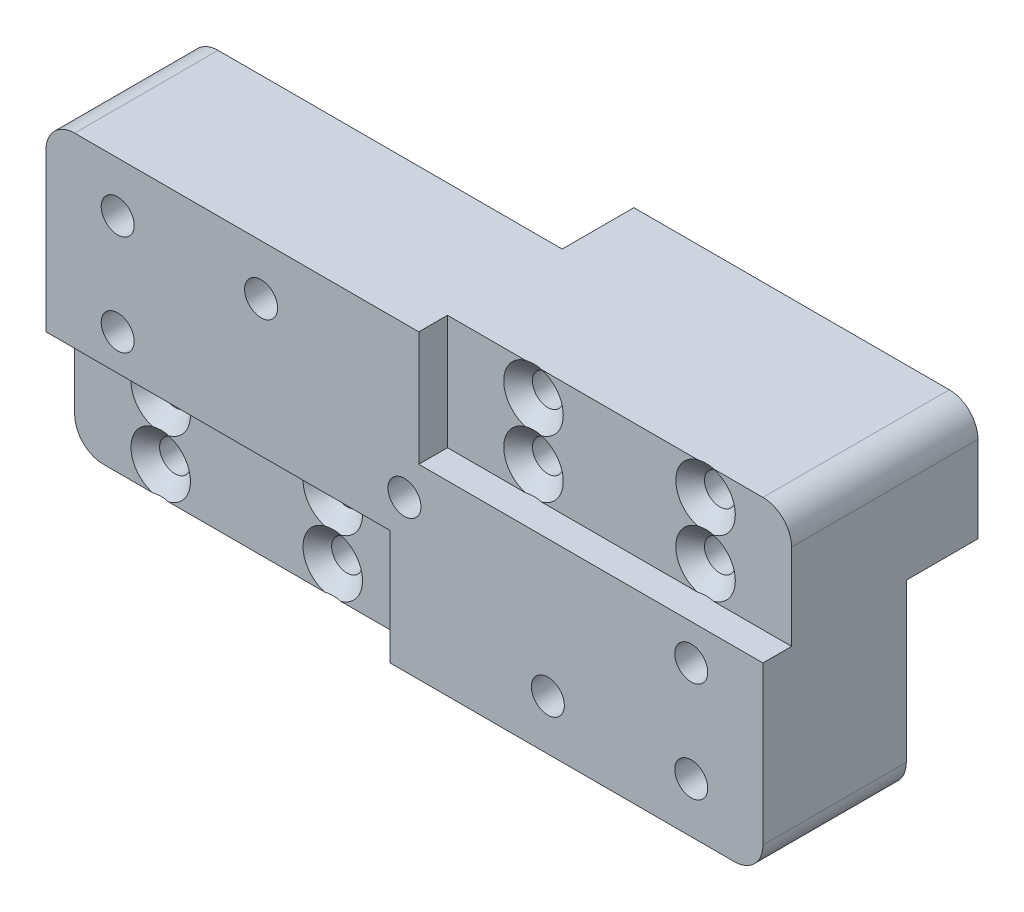
SolidWorks part; units mm, degrees
ref_plane "Front Plane" through (0, 0, 0) normal (0, 0, 1) x (1, 0, 0)
ref_plane "Top Plane" through (0, 0, 0) normal (0, 1, 0) x (1, 0, 0)
ref_plane "Right Plane" through (0, 0, 0) normal (1, 0, 0) x (0, 0, -1)
sketch "Sketch1" plane through (0, 0, 0) normal (0, 0, 1) x (1, 0, 0)
  line L0 (17.5, 10.5204) -> (17.5, 2.5204) construction
  line L1 (-20.5, -2.4796) -> (3.5, -2.4796)
  line L2 (-20.5, -2.4796) -> (-20.5, -10.4796)
  line L3 (-20.5, -10.4796) -> (3.5, -10.4796)
  line L4 (3.5, -2.4796) -> (3.5, -10.4796)
  line L5 (5.5, 10.5204) -> (29.5, 10.5204)
  line L6 (5.5, 10.5204) -> (5.5, 2.5204)
  line L7 (5.5, 2.5204) -> (29.5, 2.5204)
  line L8 (29.5, 10.5204) -> (29.5, 2.5204)
  line L9 (17.5, 6.5204) -> (5.5, 6.5204) construction
  line L10 (-8.5, -10.4796) -> (-8.5, -2.4796) construction
  line L11 (-8.5, -6.4796) -> (3.5, -6.4796) construction
  circle A0 centre (11.5, 8.5204) radius 1.075
  circle A2 centre (11.5, 4.5204) radius 1.075
  circle A3 centre (23.5, 4.5204) radius 1.075
  circle A5 centre (23.5, 8.5204) radius 1.075
  circle A7 centre (-14.5, -4.4796) radius 1.075
  circle A8 centre (-2.5, -8.4796) radius 1.075
  circle A11 centre (-14.5, -8.4796) radius 1.075
  circle A12 centre (-2.5, -4.4796) radius 1.075
  dimension "D7" = 2.15
  dimension "D15" = 2.15
  dimension "D16" = 2.15
  dimension "D17" = 2.15
  dimension "D1" = 8
  dimension "D2" = 8
  dimension "D3" = 2
  dimension "D4" = 24
  dimension "D5" = 24
  dimension "D6" = 5
  dimension "D9" = 6
  dimension "D10" = 2
  dimension "D13" = 2
extrude "Boss-Extrude1" add sketch "Sketch1" along normal blind 5
sketch "Sketch2" plane through (0, 0, 5) normal (0, 0, 1) x (1, 0, 0)
  line L1 (-20.5, -10.4796) -> (29.5, -10.4796)
  line L2 (-20.5, -10.4796) -> (-20.5, 10.5204)
  line L3 (-20.5, 10.5204) -> (29.5, 10.5204)
  line L4 (-20.5, -2.4796) -> (-20.5, -10.4796)
  line L5 (-20.5, -10.4796) -> (3.5, -10.4796)
  line L6 (3.5, -10.4796) -> (3.5, -2.4796)
  line L7 (3.5, -2.4796) -> (-20.5, -2.4796)
  line L8 (-20.5, -2.4796) -> (-20.5, -10.4796)
  line L9 (-20.5, -10.4796) -> (3.5, -10.4796)
  line L10 (3.5, -10.4796) -> (3.5, -2.4796)
  line L11 (3.5, -2.4796) -> (-20.5, -2.4796)
  line L12 (5.5, 10.5204) -> (5.5, 2.5204)
  line L13 (5.5, 2.5204) -> (29.5, 2.5204)
  line L14 (29.5, 2.5204) -> (29.5, 10.5204)
  line L15 (29.5, 10.5204) -> (5.5, 10.5204)
  line L16 (5.5, 10.5204) -> (5.5, 2.5204)
  line L17 (5.5, 2.5204) -> (29.5, 2.5204)
  line L18 (29.5, 2.5204) -> (29.5, 10.5204)
  line L19 (29.5, 10.5204) -> (5.5, 10.5204)
  line L20 (29.5, -10.4796) -> (29.5, 10.5204)
  circle A0 centre (-14.5, -8.4796) radius 1.075 construction
  circle A2 centre (-14.5, -4.4796) radius 1.075 construction
  circle A3 centre (-2.5, -8.4796) radius 1.075 construction
  circle A7 centre (11.5, 8.5204) radius 1.075 construction
  circle A8 centre (11.5, 4.5204) radius 1.075 construction
  circle A9 centre (23.5, 8.5204) radius 1.075 construction
  circle A11 centre (23.5, 4.5204) radius 1.075 construction
  circle A12 centre (23.5, 4.5204) radius 1.075
  circle A14 centre (23.5, 8.5204) radius 1.075
  circle A15 centre (11.5, 4.5204) radius 1.075
  circle A16 centre (11.5, 8.5204) radius 1.075
  circle A20 centre (-2.5, -8.4796) radius 1.075
  circle A21 centre (-14.5, -4.4796) radius 1.075
  circle A23 centre (-14.5, -8.4796) radius 1.075
  circle A24 centre (-2.5, -4.4796) radius 1.075 construction
  circle A25 centre (-2.5, -4.4796) radius 1.075
  circle M10 centre (-14.5, -8.4796) radius 1.075
  circle M11 centre (-14.5, -4.4796) radius 1.075
  line M12 (-20.5, -2.4796) -> (-20.5, -10.4796)
  line M13 (-20.5, -10.4796) -> (3.5, -10.4796)
  line M14 (3.5, -10.4796) -> (3.5, -2.4796)
  line M15 (3.5, -2.4796) -> (-20.5, -2.4796)
  circle M17 centre (-2.5, -8.4796) radius 1.075
  dimension "D1" = 0
  dimension "D2" = 0
extrude "Boss-Extrude2" add sketch "Sketch2" along normal blind 8 contours L1 L20 L17 L16 L3 L2 M15 M14 | L17 L18 L3 L16 A16 A15 A14 A12 | M15 M12 M13 M14 M10 M17 M11 region at (-8.5, -6.4796, 5) region at (4.5, 0.0204, 5) region at (17.5, 6.5204, 5)
extrude "Boss-Extrude3" add sketch "Sketch2<6>" along normal blind 10 contours L1 L20 L17 L16 L3 L2 M15 M14 region at (4.5, 0.0204, 5)
sketch "Sketch2<6>" plane through (0, 0, 5) normal (0, 0, 1) x (1, 0, 0) same geometry as "Sketch2"
chamfer "Chamfer1" distance 1 angle 45 8 edges at (12.575, 4.5204, 13) (-13.425, -4.4796, 13) (-13.425, -8.4796, 13) (-1.425, -8.4796, 13) (24.575, 4.5204, 13) (24.575, 8.5204, 13) (12.575, 8.5204, 13) (-1.425, -4.4796, 13)
sketch "Sketch3" plane through (0, 0, 15) normal (0, 0, 1) x (1, 0, 0)
  line L0 (-20.5, 10.5204) -> (29.5, -10.4796) construction
  line L1 (4.5, 0.0204) -> (-20.5, 0.0204) construction
  line L2 (-20.5, 0.0204) -> (29.5, 0.0204) construction
  line L3 (-20.5, 7.0204) -> (5.5, 7.0204) construction
  line L4 (3.5, -6.9796) -> (29.5, -6.9796) construction
  line L5 (-15.5, 0.0204) -> (-15.5, 7.0204) construction
  line L6 (-5.5, 7.0204) -> (-5.5, 2.0204) construction
  line L7 (14.5, -1.9796) -> (14.5, -6.9796) construction
  line L8 (3.5, -10.4796) -> (29.5, -10.4796)
  line L9 (29.5, -10.4796) -> (29.5, 2.5204)
  line L10 (29.5, 2.5204) -> (5.5, 2.5204)
  line L11 (5.5, 2.5204) -> (5.5, 10.5204)
  line L12 (5.5, 10.5204) -> (-20.5, 10.5204)
  line L13 (-20.5, 10.5204) -> (-20.5, -2.4796)
  line L14 (-20.5, -2.4796) -> (3.5, -2.4796)
  line L15 (3.5, -2.4796) -> (3.5, -10.4796)
  line L16 (3.5, -10.4796) -> (29.5, -10.4796)
  line L17 (29.5, -10.4796) -> (29.5, 2.5204)
  line L18 (29.5, 2.5204) -> (5.5, 2.5204)
  line L19 (5.5, 2.5204) -> (5.5, 10.5204)
  line L20 (5.5, 10.5204) -> (-20.5, 10.5204)
  line L21 (-20.5, 10.5204) -> (-20.5, -2.4796)
  line L22 (-20.5, -2.4796) -> (3.5, -2.4796)
  line L23 (3.5, -2.4796) -> (3.5, -10.4796)
  line L24 (24.5, 0.0204) -> (24.5, -6.9796) construction
  circle A0 centre (4.5, 0.0204) radius 1.15
  circle A2 centre (24.5, 0.0204) radius 1.15
  circle A4 centre (-15.5, 0.0204) radius 1.15
  circle A5 centre (-15.5, 7.0204) radius 1.15
  circle A6 centre (-5.5, 7.0204) radius 1.15
  circle A7 centre (14.5, -6.9796) radius 1.15
  circle A8 centre (24.5, -6.9796) radius 1.15
  arc A9 (-6.65, 0.0204) -> (-4.35, 0.0204) centre (-5.5, 0.0204) ccw [skipped]
  arc A10 (13.35, 0.0204) -> (14.5, -1.1296) centre (14.5, 0.0204) ccw [skipped]
  dimension "D2" = 2.3
  dimension "D6" = 2.3
  dimension "D7" = 2.3
  dimension "D10" = 2.3
  dimension "D11" = 2.3
  dimension "D5" = 7
  dimension "6" = 7
  dimension "D1" = 0
  dimension "D3" = 3
  dimension "D4" = 3
fillet "Fillet1" radius 2 4 edges at (-20.5, -10.4796, 6.5) (29.5, -10.4796, 10) (29.5, 10.5204, 6.5) (-20.5, 10.5204, 10)
extrude "Cut-Extrude1" cut sketch "Sketch3" against normal blind 7 contours A4 | A5 | A6 | A0 | A7 | A2 | A8 region at (-15.5, 0.0204, 15)
